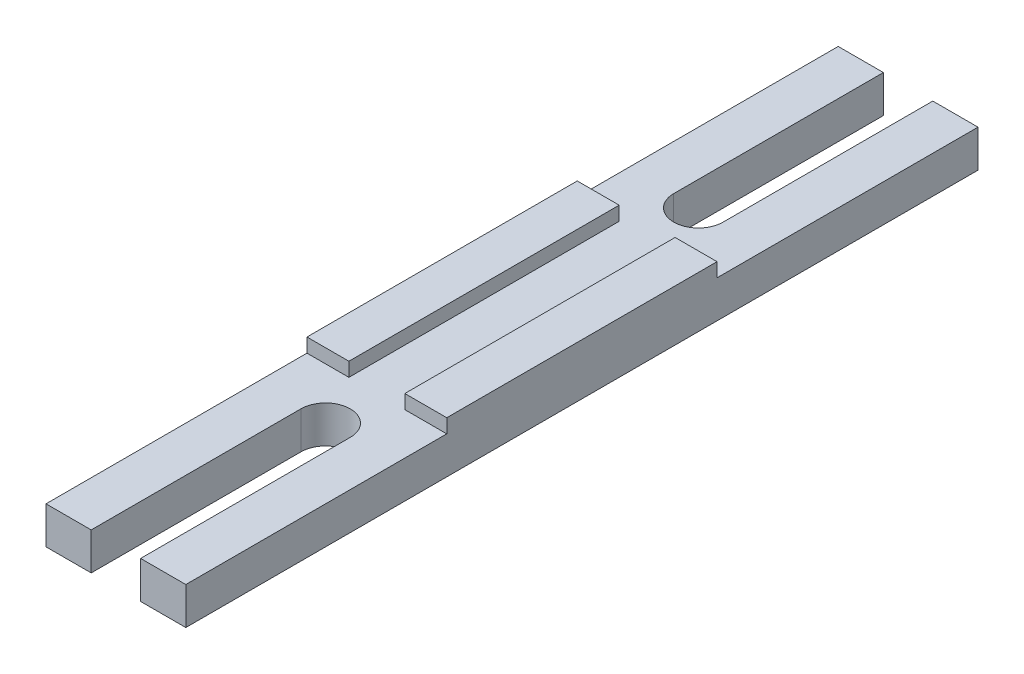
SolidWorks part; units mm, degrees
ref_plane "Front Plane" through (0, 0, 0) normal (0, 0, 1) x (1, 0, 0)
ref_plane "Top Plane" through (0, 0, 0) normal (0, 1, 0) x (1, 0, 0)
ref_plane "Right Plane" through (0, 0, 0) normal (1, 0, 0) x (0, 0, -1)
sketch "Sketch1" plane through (0, 0, 0) normal (1, 0, 0) x (0, 0, -1)
  line L0 (0, 0) -> (0, 23)
  line L1 (0, 23) -> (20, 23)
  line L2 (20, 23) -> (30, 6)
  line L3 (30, 0) -> (0, 0)
  line L4 (30, 6) -> (30, 0)
  dimension "D1" = 23
  dimension "D2" = 30
  dimension "D3" = 20
  dimension "D4" = 6
extrude "Boss-Extrude1" add sketch "Sketch1" along normal mid plane 6.35
sketch "Sketch2" plane through (0, 0, 0) normal (0, -1, 0) x (1, 0, 0)
  line L0 (3.175, 0) -> (-3.175, -30) construction
  line L1 (7.5, -42.5) -> (-7.5, -42.5)
  line L2 (7.5, -42.5) -> (7.5, 12.5)
  line L3 (7.5, 12.5) -> (-7.5, 12.5)
  line L4 (-7.5, -42.5) -> (-7.5, 12.5)
  line L5 (7.5, -42.5) -> (-7.5, 12.5) construction
  line L6 (7.5, 12.5) -> (-7.5, -42.5) construction
  point P0 (0, -15)
  dimension "D1" = 15
  dimension "D2" = 55
extrude "Boss-Extrude2" add sketch "Sketch2" against normal blind 5.5
sketch "Sketch3" plane through (0, 5.5, 0) normal (0, 1, 0) x (1, 0, 0)
  line L0 (-7.5, 15) -> (7.5, 15) construction
  line L1 (-7.5, -12.5) -> (-7.5, 42.5) construction
  line L2 (7.5, 42.5) -> (7.5, -12.5) construction
  line L3 (0, 45) -> (0, 35) construction
  line L4 (2.65, 45) -> (2.65, 35)
  line L5 (-2.65, 45) -> (-2.65, 35)
  line L7 (0, -15) -> (0, -5) construction
  line L8 (2.65, -15) -> (2.65, -5)
  line L9 (-2.65, -15) -> (-2.65, -5)
  arc A0 (2.65, 45) -> (-2.65, 45) centre (0, 45) ccw
  arc A1 (-2.65, 35) -> (2.65, 35) centre (0, 35) ccw
  arc A2 (2.65, -15) -> (-2.65, -15) centre (0, -15) cw
  arc A3 (-2.65, -5) -> (2.65, -5) centre (0, -5) cw
  point P9 (0, 40)
  point P19 (0, -10)
  dimension "D1" = 5.3
  dimension "D2" = 10
  dimension "D3" = 20
extrude "Cut-Extrude1" cut sketch "Sketch3" against normal through all
fillet "Fillet1" radius 20 1 edges at (0, 23, -20)
sketch "Sketch6" plane through (3.175, 0, 0) normal (1, 0, 0) x (0, 0, -1)
  line L0 (30, 5.5) -> (0, 5.5) construction
  line L1 (0, 23) -> (31.6168, 23)
  line L2 (0, 23) -> (0, 5.5)
  line L3 (0, 5.5) -> (31.6168, 5.5)
  line L4 (31.6168, 23) -> (31.6168, 5.5)
extrude "Cut-Extrude3" cut sketch "Sketch6" against normal through all
sketch "Sketch7" plane through (0, 0, 0) normal (1, 0, 0) x (0, 0, -1)
  line L0 (15, 0) -> (15, 30.0187) construction
  line L1 (42.5, 0) -> (-12.5, 0) construction
  line L2 (0.5, 5.5) -> (0.5, 15.106)
  line L3 (42.5, 5.5) -> (-12.5, 5.5) construction
  line L4 (0.5, 15.106) -> (24.2538, 15.106)
  line L5 (24.2538, 15.106) -> (24.2538, 23.5588)
  line L6 (24.2538, 23.5588) -> (33.9025, 23.5588)
  line L7 (33.9025, 23.5588) -> (33.9025, 12.7721)
  line L8 (33.9025, 12.7721) -> (29.5, 12.7721)
  line L9 (29.5, 12.7721) -> (29.5, 5.5)
  line L11 (29.5, 5.5) -> (15, 5.5)
  line L12 (15, 5.5) -> (0.5, 5.5)
  dimension "D1" = 29
extrude "Boss-Extrude4" add sketch "Sketch7" along normal mid plane 6
fillet "Fillet3" radius 5 3 edges at (0, 12.7721, -29.5) (0, 15.106, -24.2538) (0, 15.106, -0.5)
sketch "Sketch9" plane through (7.5, 0, 0) normal (1, 0, 0) x (0, 0, -1)
  line L0 (42.5, 5.5) -> (-12.5, 5.5) construction
  line L1 (-12.5, 5.5) -> (0.5, 5.5)
  line L2 (-12.5, 5.5) -> (-12.5, 4)
  line L3 (-12.5, 4) -> (0.5, 4)
  line L4 (0.5, 5.5) -> (0.5, 4)
  line L5 (0.5, 10.106) -> (0.5, 5.5) construction
  line L6 (42.5, 0) -> (-12.5, 0) construction
  line L7 (15, 0) -> (15, 5.5) construction
  line L8 (0.5, 5.5) -> (29.5, 5.5) construction
  line L9 (29.5, 5.5) -> (29.5, 4)
  line L10 (42.5, 4) -> (29.5, 4)
  line L11 (42.5, 5.5) -> (42.5, 4)
  line L12 (42.5, 5.5) -> (29.5, 5.5)
  dimension "D1" = 4
extrude "Cut-Extrude4" cut sketch "Sketch9" against normal through all
sketch "Sketch11" plane through (0, 0, -29.5) normal (0, 0, -1) x (-1, 0, 0)
  line L0 (-3, 7.808) -> (-3, 4)
  line L1 (7.5, 4) -> (-7.5, 4) construction
  line L2 (-3, 4) -> (3, 4)
  line L3 (7.5, 4) -> (2.65, 4) construction
  line L4 (3, 4) -> (3, 7.808)
split "Split1" trim tools "Sketch11" bodies to split 108 resulting bodies 109 110
sketch "Sketch12" plane through (0, 4, 0) normal (0, 1, 0) x (1, 0, 0)
  line L0 (2.65, -12.5) -> (2.65, -5) construction
  line L1 (-7.5, 42.5) -> (-2.65, 42.5)
  line L2 (-7.5, 42.5) -> (-7.5, 57.5)
  line L3 (-7.5, 57.5) -> (-2.65, 57.5)
  line L4 (-2.65, 42.5) -> (-2.65, 57.5)
  line L5 (2.65, 42.5) -> (7.5, 42.5)
  line L6 (2.65, 42.5) -> (2.65, 57.5)
  line L7 (2.65, 57.5) -> (7.5, 57.5)
  line L8 (7.5, 42.5) -> (7.5, 57.5)
  line L9 (-2.65, -12.5) -> (-7.5, -12.5)
  line L10 (-2.65, -12.5) -> (-2.65, -27.5)
  line L11 (-2.65, -27.5) -> (-7.5, -27.5)
  line L12 (-7.5, -12.5) -> (-7.5, -27.5)
  line L13 (7.5, -12.5) -> (2.65, -12.5)
  line L14 (7.5, -12.5) -> (7.5, -27.5)
  line L15 (7.5, -27.5) -> (2.65, -27.5)
  line L16 (2.65, -12.5) -> (2.65, -27.5)
  line L17 (-2.65, -5) -> (-2.65, -12.5) construction
  line L18 (2.65, 35) -> (2.65, 42.5) construction
  line L19 (-2.65, 42.5) -> (-2.65, 35) construction
  line L20 (-2.65, 57.5) -> (2.65, 57.5) construction
  line L21 (-2.65, -27.5) -> (2.65, -27.5) construction
  line L22 (7.5, 29.5) -> (7.5, 42.5) construction
  line L23 (-7.5, -12.5) -> (-7.5, 0.5) construction
  circle A0 centre (0, -5) radius 2.5 construction
  circle A1 centre (0, -10) radius 2.5 construction
  circle A2 centre (0, -15) radius 2.5 construction
  circle A3 centre (0, -20) radius 2.5 construction
  circle A4 centre (0, -25) radius 2.5 construction
  dimension "D2" = 5
  dimension "D1" = 85
  dimension "D3" = 5
extrude "Boss-Extrude5" add sketch "Sketch12" against normal up to surface (4 mm away) up to face at (0, 0, -15)
delete or keep bodies "Body-Delete/Keep 1" type delete bodies bodies 110
delete or keep bodies "Body-Delete/Keep 2" [suppressed] type delete bodies bodies 109
